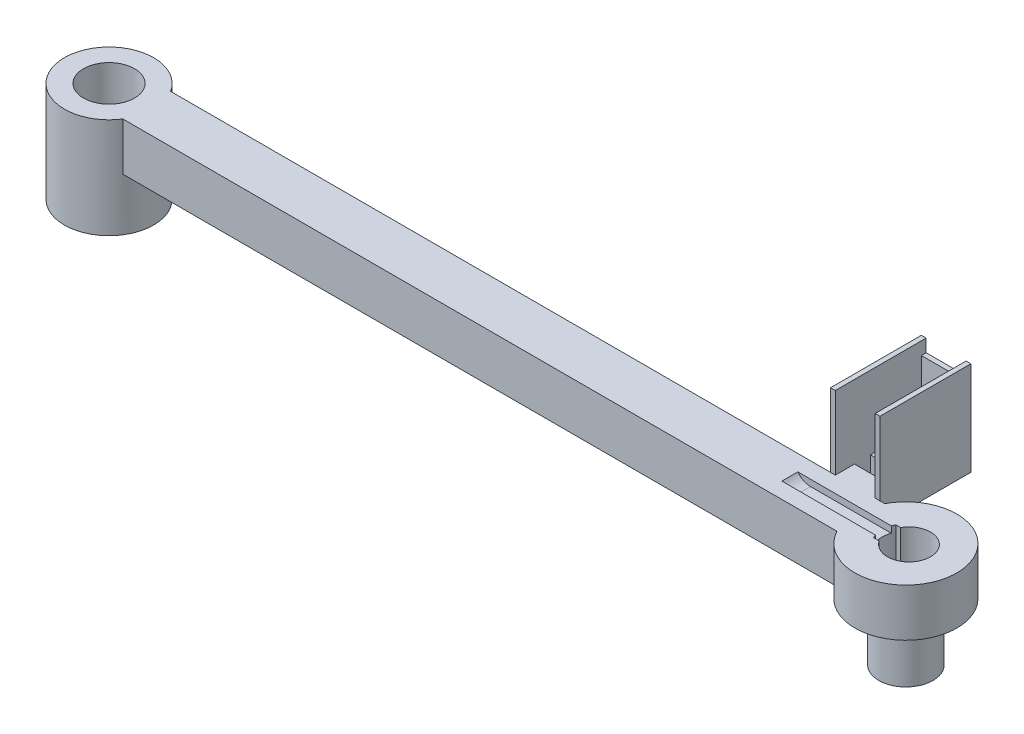
SolidWorks part; units mm, degrees
note: The reader was unsure of these and kept them because the rebuilt part matched: shared geometry of "Sketch2<9>", "Sketch2<13>", "Sketch2<14>", "Sketch18<3>".
ref_plane "Front Plane" through (0, 0, 0) normal (0, 0, 1) x (1, 0, 0)
ref_plane "Top Plane" through (0, 0, 0) normal (0, 1, 0) x (1, 0, 0)
ref_plane "Right Plane" through (0, 0, 0) normal (1, 0, 0) x (0, 0, -1)
sketch "Sketch2" plane through (0, 0, 0) normal (0, 1, 0) x (1, 0, 0)
  line L0 (200, 3.2206) -> (178.0009, 3.2206) construction
  line L1 (207.5, 11.0371) -> (207.5, -4.5958) construction
  line L15 (196.3443, 6.7206) -> (193.3668, 6.7206)
  line L16 (196.3443, 6.7206) -> (196.3443, -0.2794)
  line L17 (196.3443, -0.2794) -> (193.3668, -0.2794)
  line L18 (193.3668, 6.7206) -> (193.3668, -0.2794)
  line L19 (196.3443, 6.7206) -> (193.3668, -0.2794) construction
  line L20 (196.3443, -0.2794) -> (193.3668, 6.7206) construction
  circle A0 centre (-50, 3.2206) radius 14
  circle A1 centre (200, 3.2206) radius 16
  circle A2 centre (200, 3.2206) radius 7.5
  circle A4 centre (-50, 3.2206) radius 8
  circle A5 centre (-50, 3.2206) radius 4.25
  circle A6 centre (200, 3.2206) radius 8.5
  circle A9 centre (200.75, 3.4458) radius 6.75
  arc A10 (192.9199, 5.6948) -> (192.9199, 0.7465) centre (200, 3.2206) ccw
  point P0 (194.8555, 3.2206)
  point P12 (192.5, 3.2206)
  point P20 (207.5, 3.2206)
  point P26 (207.5, 3.2206)
  dimension "D1" = 28
  dimension "D2" = 32
  dimension "D3" = 15
  dimension "D4" = 8.5
  dimension "D5" = 17
  dimension "D6" = 16
  dimension "D7" = 8.5
  dimension "D8" = 1
  dimension "D9" = 13.5
  dimension "D10" = 7
extrude "Boss-Extrude7" add sketch "Sketch2" along normal blind 15 and the other way blind 16.5 contours A0
extrude "Boss-Extrude8" add sketch "Sketch2<9>" along normal blind 15 separate body contours A1 | A6 A2 | A9 L17 A2 | A9 A2 L15
sketch "Sketch2<9>" plane through (0, 0, 0) normal (0, 1, 0) x (1, 0, 0) same geometry as "Sketch2"
sketch "Sketch3" plane through (0, 0, 0) normal (1, 0, 0) x (0, 0, -1)
  line L1 (10.7206, 15) -> (-4.2794, 15)
  line L2 (10.7206, 15) -> (10.7206, 0)
  line L3 (10.7206, 0) -> (-4.2794, 0)
  line L4 (-4.2794, 15) -> (-4.2794, 0)
  line L7 (-1.2794, 12) -> (7.7206, 12)
  line L8 (-1.2794, 12) -> (-1.2794, 0)
  line L9 (-1.2794, 0) -> (7.7206, 0)
  line L10 (7.7206, 12) -> (7.7206, 0)
  line L12 (17.2206, -16.5) -> (17.2206, 15) construction
  line L13 (-10.7794, 15) -> (-10.7794, -16.5) construction
  line L14 (19.2206, 0) -> (19.2206, 15) construction
  line L15 (-12.7794, 15) -> (-12.7794, 0) construction
  dimension "D1" = 15
  dimension "D2" = 15
  dimension "D3" = 6.5
  dimension "D4" = 6.5
  dimension "D5" = 9
  dimension "D6" = 12
  dimension "D7" = 8.5
  dimension "D8" = 3
  dimension "D9" = 3
  dimension "D10" = 3
  dimension "D11" = 8.5
extrude "Boss-Extrude11" add sketch "Sketch3" against normal up to body and the other way up to body separate body contours L7 L10 L3 L2 L1 L4 L8
sketch "Sketch15" plane through (0, 0, -7.7206) normal (0, 0, 1) x (1, 0, 0)
  line L0 (-36.7429, 0) -> (184.6458, 0) construction
  line L1 (-15.9512, 12) -> (-12.9512, 12)
  line L2 (-15.9512, 12) -> (-15.9512, 2.5)
  line L3 (-15.9512, 2.5) -> (-12.9512, 2.5)
  line L4 (-12.9512, 12) -> (-12.9512, 2.5)
  line L5 (-38.1784, 0) -> (185.8667, 0) construction
  line L7 (84.9578, 12) -> (87.9578, 12)
  line L8 (12.2761, 12) -> (9.2761, 12)
  line L9 (12.2761, 12) -> (12.2761, 2.5)
  line L10 (12.2761, 2.5) -> (9.2761, 2.5)
  line L11 (9.2761, 12) -> (9.2761, 2.5)
  line L12 (34.5033, 12) -> (37.5033, 12)
  line L13 (34.5033, 12) -> (34.5033, 2.5)
  line L14 (34.5033, 2.5) -> (37.5033, 2.5)
  line L15 (37.5033, 12) -> (37.5033, 2.5)
  line L16 (59.7305, 12) -> (62.7305, 12)
  line L17 (59.7305, 12) -> (59.7305, 2.5)
  line L18 (59.7305, 2.5) -> (62.7305, 2.5)
  line L19 (62.7305, 12) -> (62.7305, 2.5)
  line L20 (-38.1784, 15) -> (-38.1784, 0) construction
  line L21 (84.9578, 12) -> (84.9578, 2.5)
  line L22 (84.9578, 2.5) -> (87.9578, 2.5)
  line L23 (87.9578, 12) -> (87.9578, 2.5)
  line L24 (110.185, 12) -> (113.185, 12)
  line L25 (110.185, 12) -> (110.185, 2.5)
  line L26 (110.185, 2.5) -> (113.185, 2.5)
  line L27 (113.185, 12) -> (113.185, 2.5)
  line L28 (135.4122, 12) -> (138.4122, 12)
  line L29 (135.4122, 12) -> (135.4122, 2.5)
  line L30 (135.4122, 2.5) -> (138.4122, 2.5)
  line L31 (138.4122, 12) -> (138.4122, 2.5)
  line L32 (160.6395, 12) -> (163.6395, 12)
  line L33 (160.6395, 12) -> (160.6395, 2.5)
  line L34 (160.6395, 2.5) -> (163.6395, 2.5)
  line L35 (163.6395, 12) -> (163.6395, 2.5)
  line L36 (185.8667, 0) -> (185.8667, 15) construction
  point P22 (10.7761, 2.5)
  dimension "D1" = 3
  dimension "D2" = 9.5
  dimension "D3" = 2.5
  dimension "D4" = 22.2272
  dimension "D5" = 22.2272
  dimension "D6" = 3
  dimension "D7" = 9.5
  dimension "D8" = 3
  dimension "D9" = 9.5
  dimension "D10" = 3
  dimension "D11" = 9.5
  dimension "D12" = 2.5
  dimension "D13" = 2.5
  dimension "D14" = 2.5
  dimension "D15" = 22.2272
  dimension "D16" = 22.2272
  dimension "D17" = 3
  dimension "D18" = 9.5
  dimension "D19" = 3
  dimension "D20" = 9.5
  dimension "D21" = 3
  dimension "D22" = 9.5
  dimension "D23" = 3
  dimension "D24" = 9.5
  dimension "D25" = 2.5
  dimension "D26" = 2.5
  dimension "D27" = 2.5
  dimension "D28" = 2.5
  dimension "D29" = 22.2272
  dimension "D30" = 22.2272
  dimension "D31" = 22.2272
  dimension "D32" = 22.2272
  dimension "D33" = 22.2272
extrude "Boss-Extrude12" add sketch "Sketch15" along normal up to next
fillet "Fillet1" radius 2 32 edges at (62.7305, 7.25, -7.7206) (62.7305, 7.25, 1.2794) (59.7305, 7.25, -7.7206) (59.7305, 7.25, 1.2794) (37.5033, 7.25, -7.7206) (37.5033, 7.25, 1.2794) (34.5033, 7.25, -7.7206) (34.5033, 7.25, 1.2794) (12.2761, 7.25, -7.7206) (12.2761, 7.25, 1.2794) (9.2761, 7.25, -7.7206) (9.2761, 7.25, 1.2794) (-12.9512, 7.25, -7.7206) (-12.9512, 7.25, 1.2794) (-15.9512, 7.25, -7.7206) (-15.9512, 7.25, 1.2794) (163.6395, 7.25, -7.7206) (163.6395, 7.25, 1.2794) (160.6395, 7.25, -7.7206) (160.6395, 7.25, 1.2794) (138.4122, 7.25, -7.7206) (138.4122, 7.25, 1.2794) (135.4122, 7.25, -7.7206) (135.4122, 7.25, 1.2794) (113.185, 7.25, -7.7206) (113.185, 7.25, 1.2794) (110.185, 7.25, -7.7206) (110.185, 7.25, 1.2794) (87.9578, 7.25, -7.7206) (87.9578, 7.25, 1.2794) (84.9578, 7.25, -7.7206) (84.9578, 7.25, 1.2794)
extrude "Boss-Extrude13" add sketch "Sketch2<13>" against normal through all from offset 4 contours A4 A5 offset against normal yes
sketch "Sketch2<13>" plane through (0, 0, 0) normal (0, 1, 0) x (1, 0, 0) same geometry as "Sketch2"
extrude "Boss-Extrude14" add sketch "Sketch2<14>" against normal blind 18 separate body contours A6 A2 | A9 L17 A2 | A9 A2 L15
sketch "Sketch2<14>" plane through (0, 0, 0) normal (0, 1, 0) x (1, 0, 0) same geometry as "Sketch2"
sketch "Sketch16" plane through (0, 15, 0) normal (0, 1, 0) x (1, 0, 0)
  line L0 (200, 3.2206) -> (178.6574, 3.2206) construction
  line L1 (163.5954, 5.7206) -> (193.5954, 5.7206)
  line L2 (163.5954, 5.7206) -> (163.5954, 0.7206)
  line L3 (163.5954, 0.7206) -> (193.5954, 0.7206)
  line L4 (193.5954, 5.7206) -> (193.5954, 0.7206)
  dimension "D1" = 5
  dimension "D2" = 30
extrude "Cut-Extrude1" cut sketch "Sketch16" against normal blind 2
fillet "Fillet2" radius 5 1 edges at (163.5954, 13, -3.2206)
sketch "Sketch18" plane through (0, 0, -10.7206) normal (0, 0, -1) x (-1, 0, 0)
  line L0 (38.1784, 15) -> (-185.8667, 15) construction
  line L1 (-184.3667, 8.5) -> (-168.8667, 8.5)
  line L2 (-184.3667, 8.5) -> (-184.3667, 38)
  line L3 (-184.3667, 38) -> (-168.8667, 38)
  line L4 (-168.8667, 8.5) -> (-168.8667, 38)
  line L5 (-182.8667, 38) -> (-170.3667, 38)
  line L6 (-182.8667, 38) -> (-182.8667, 10)
  line L7 (-182.8667, 10) -> (-170.3667, 10)
  line L8 (-170.3667, 38) -> (-170.3667, 10)
  line L9 (-182.8667, 10) -> (-170.3667, 10)
  line L10 (-182.8667, 10) -> (-182.8667, 15)
  line L11 (-182.8667, 15) -> (-170.3667, 15)
  line L12 (-170.3667, 10) -> (-170.3667, 15)
  line L13 (-185.8667, 0) -> (-185.8667, 15) construction
  line M9 (38.1784, 15) -> (-185.8667, 15)
  dimension "D1" = 29.5
  dimension "D2" = 15.5
  dimension "D3" = 28
  dimension "D4" = 12.5
  dimension "D5" = 1.5
  dimension "D6" = 5
  dimension "D7" = 0
  dimension "D8" = 1.5
extrude "Boss-Extrude15" add sketch "Sketch18" along normal blind 28.5 contours L6 L3 L2 M9 | L8 L7 L6 L2 L1 L4 M9 | L3 L8 L4 M9
extrude "Boss-Extrude16" add sketch "Sketch18<3>" along normal blind 6 contours L8 L6 L7 M9
sketch "Sketch18<3>" plane through (0, 0, -10.7206) normal (0, 0, -1) x (-1, 0, 0) same geometry as "Sketch18"
sketch "Sketch19" plane through (0, 10, 0) normal (0, 1, 0) x (1, 0, 0)
  line L0 (182.8667, 39.2206) -> (182.8667, 16.7206) construction
  line L1 (170.3667, 39.2206) -> (182.8667, 39.2206)
  line L2 (170.3667, 39.2206) -> (170.3667, 37.7206)
  line L3 (170.3667, 37.7206) -> (182.8667, 37.7206)
  line L4 (182.8667, 39.2206) -> (182.8667, 37.7206)
  dimension "D1" = 1.5
extrude "Boss-Extrude17" add sketch "Sketch19" along normal blind 24
sketch "Sketch20" plane through (0, 10, 0) normal (0, 1, 0) x (1, 0, 0)
  line L0 (182.8667, 37.7206) -> (182.8667, 16.7206) construction
  line L1 (170.3667, 37.7206) -> (182.8667, 37.7206)
  line L2 (170.3667, 37.7206) -> (170.3667, 21.7206)
  line L3 (170.3667, 21.7206) -> (182.8667, 21.7206)
  line L4 (182.8667, 37.7206) -> (182.8667, 21.7206)
  dimension "D1" = 16
extrude "Boss-Extrude18" add sketch "Sketch20" along normal blind 5
